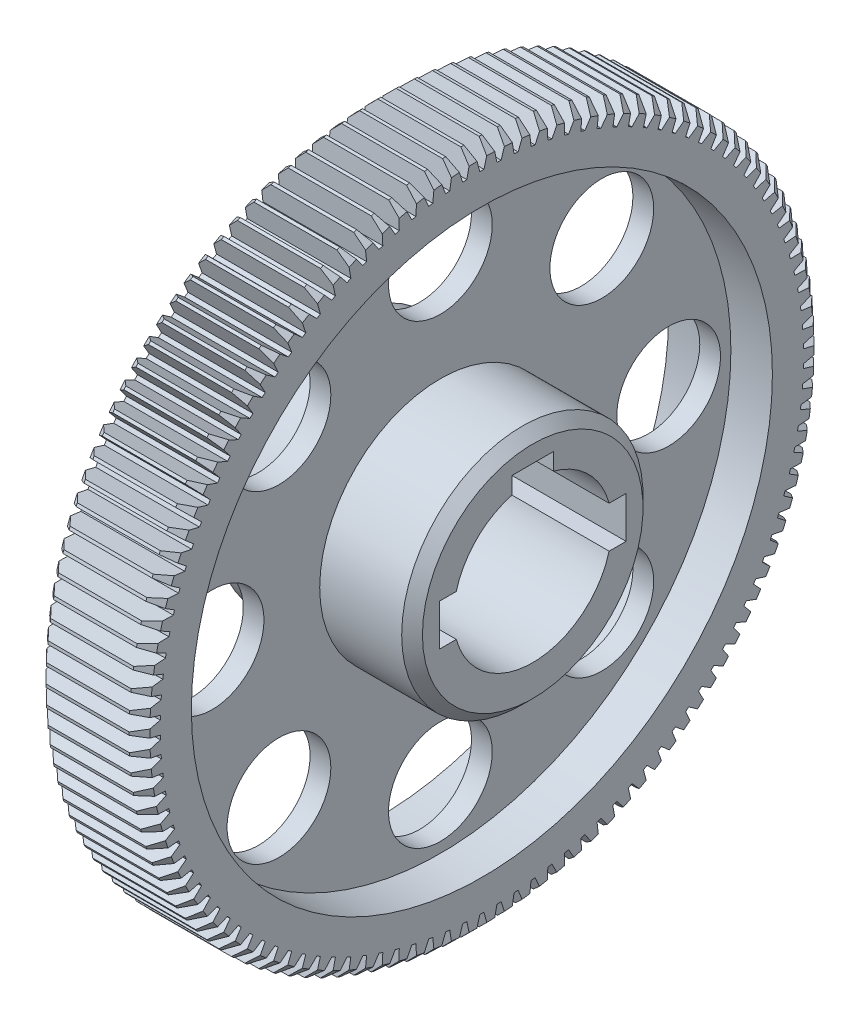
SolidWorks part; units mm, degrees
ref_plane "前视基准面" through (0, 0, 0) normal (0, 0, 1) x (1, 0, 0)
ref_plane "上视基准面" through (0, 0, 0) normal (0, 1, 0) x (1, 0, 0)
ref_plane "右视基准面" through (0, 0, 0) normal (1, 0, 0) x (0, 0, -1)
other "Configuration Table"
sketch "草图2" plane through (0, 0, 0) normal (0, 1, 0) x (1, 0, 0)
  line L0 (0, 0) -> (302.3862, 0) construction
  line L1 (0, 0) -> (0, 165) construction
  line L2 (-25, 165) -> (25, 165)
  line L3 (25, 165) -> (25, 140)
  line L4 (25, 140) -> (5, 140)
  line L5 (5, 140) -> (5, 58.15)
  line L6 (5, 58.15) -> (49.5, 58.15)
  line L11 (-5, 58.15) -> (-49.5, 58.15)
  line L12 (-5, 140) -> (-5, 58.15)
  line L13 (-25, 140) -> (-5, 140)
  line L14 (-25, 165) -> (-25, 140)
  line L15 (49.5, 58.15) -> (49.5, 38.15)
  line L16 (49.5, 38.15) -> (-49.5, 38.15)
  line L17 (-49.5, 38.15) -> (-49.5, 58.15)
  dimension "D1" = 76.3
  dimension "D2" = 330
  dimension "D3" = 25
  dimension "D4" = 10
  dimension "D5" = 50
  dimension "D6" = 20
  dimension "D7" = 99
revolve "旋转1" add sketch "草图2" angle 360 about L0
chamfer "倒角1" distance 5 angle 45 4 edges at (-49.5, 0, 58.15) (49.5, 0, 58.15) (-25, 0, 165) (25, 0, 165)
sketch "草图3" plane through (5, 0, 0) normal (1, 0, 0) x (0, 0, -1)
  circle A0 centre (0, 110) radius 25
  circle A1 centre (77.7817, 77.7817) radius 25
  circle A2 centre (110, 0) radius 25
  circle A3 centre (77.7817, -77.7817) radius 25
  circle A4 centre (0, -110) radius 25
  circle A5 centre (-77.7817, -77.7817) radius 25
  circle A6 centre (-110, 0) radius 25
  circle A7 centre (-77.7817, 77.7817) radius 25
  point P19 (0, 0)
  dimension "D1" = 50
  dimension "D2" = 110
  dimension "D3" = 8
extrude "切除-拉伸1" cut sketch "草图3" against normal blind 10
sketch "草图4" plane through (-49.5, 0, 0) normal (-1, 0, 0) x (0, 0, 1)
  line L1 (-10, 45) -> (10, 45)
  line L2 (-10, 45) -> (-10, 0)
  line L3 (-10, 0) -> (10, 0)
  line L4 (10, 45) -> (10, 0)
  line L5 (-10, 45) -> (10, 0) construction
  line L6 (-10, 0) -> (10, 45) construction
  circle A0 centre (0, 0) radius 53.15 construction
  point P0 (0, 22.5)
  dimension "D1" = 20
  dimension "D2" = 45
extrude "切除-拉伸2" cut sketch "草图4" against normal up to next
pattern_circular "阵列(圆周)1" count 4 over 360 about axis through (0, 0, 0) along (-1, 0, 0) skipping 2 of "切除-拉伸2" reverse direction yes
sketch "草图5" plane through (25, 0, 0) normal (1, 0, 0) x (0, 0, -1)
  line L0 (0, 0) -> (0, 230.2447) construction
  line L1 (-1, 154.9968) -> (-3.6694, 164.9592)
  line L2 (1, 154.9968) -> (3.6694, 164.9592)
  arc A0 (1, 154.9968) -> (-1, 154.9968) centre (0, 0) ccw
  circle A1 centre (0, 0) radius 165 construction
  arc A2 (3.6694, 164.9592) -> (-3.6694, 164.9592) centre (0, 0) ccw
  dimension "D1" = 310
  dimension "D2" = 15
  dimension "D3" = 1
extrude "切除-拉伸3" cut sketch "草图5" against normal up to next
pattern_circular "阵列(圆周)2" count 118 over 360 about axis through (0, 0, 0) along (-1, 0, 0) of "切除-拉伸3"
equation "\"R\"=330"
equation "\"D2@草图2\"=\"R\""
